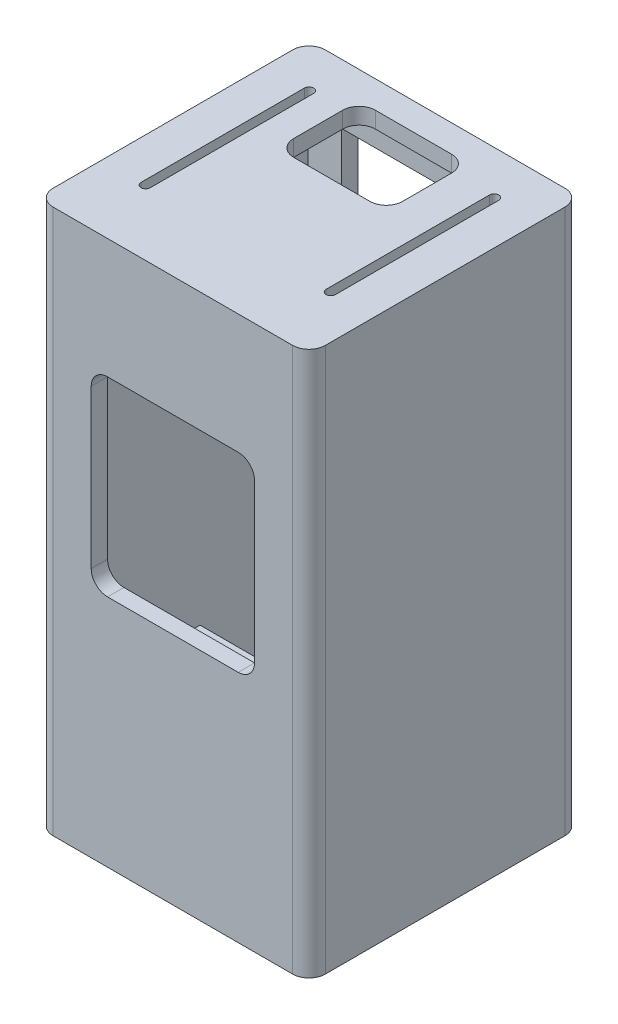
SolidWorks part; units mm, degrees
ref_plane "前视基准面" through (0, 0, 0) normal (0, 0, 1) x (1, 0, 0)
ref_plane "上视基准面" through (0, 0, 0) normal (0, 1, 0) x (1, 0, 0)
ref_plane "右视基准面" through (0, 0, 0) normal (1, 0, 0) x (0, 0, -1)
sketch "草图1" plane through (0, 0, 0) normal (0, 1, 0) x (1, 0, 0)
  line L1 (-25, 25) -> (25, 25)
  line L2 (-25, 25) -> (-25, -25)
  line L3 (-25, -25) -> (25, -25)
  line L4 (25, 25) -> (25, -25)
  point P4 (0, 0)
  dimension "D1" = 50
  dimension "D2" = 50
  dimension "D3" = 25
  dimension "D4" = 25
extrude "凸台-拉伸2" add sketch "草图1" along normal blind 100 contours L2 L1 L4 L3
fillet "圆角4" radius 3 4 edges at (25, 50, -25) (-25, 50, -25) (-25, 50, 25) (25, 50, 25)
sketch "草图3" plane through (0, 0, 0) normal (0, 1, 0) x (1, 0, 0)
  line L0 (-27.5, 0) -> (27.5, 0) construction
  line L1 (-22, 22) -> (22, 22)
  line L2 (-22, 22) -> (-22, -22)
  line L3 (-22, -22) -> (22, -22)
  line L4 (22, 22) -> (22, -22)
  dimension "D1" = 22
  dimension "D2" = 22
  dimension "D3" = 22
  dimension "D4" = 22
extrude "切除-拉伸4" cut sketch "草图3" along normal blind 80
extrude "凸台-拉伸4" add sketch "草图3<4>" along normal blind 20
sketch "草图3<4>" plane through (0, 0, 0) normal (0, 1, 0) x (1, 0, 0) same geometry as "草图3"
sketch "草图7" plane through (0, 0, 0) normal (0, 1, 0) x (1, 0, 0)
  line L0 (-22, 22) -> (-22, -22) construction
  line L1 (-22, -2) -> (22, -2)
  line L2 (-22, -2) -> (-22, -22)
  line L3 (-22, -22) -> (22, -22)
  line L4 (22, -2) -> (22, -22)
  dimension "D1" = 2
  dimension "D2" = 20
  dimension "D3" = 44
  dimension "D4" = 0
extrude "切除-拉伸5" cut sketch "草图7" along normal blind 20
extrude "凸台-拉伸5" add sketch "草图7<2>" along normal blind 5
sketch "草图7<2>" plane through (0, 0, 0) normal (0, 1, 0) x (1, 0, 0) same geometry as "草图7"
sketch "草图9" plane through (0, 0, 0) normal (0, 1, 0) x (1, 0, 0)
  line L0 (-22, 22) -> (-22, -22) construction
  line L1 (-22, 22) -> (22, 22)
  line L2 (-22, 22) -> (-22, 2)
  line L3 (-22, 2) -> (22, 2)
  line L4 (22, 22) -> (22, 2)
  point P4 (0, 2)
  dimension "D1" = 44
  dimension "D2" = 2
  dimension "D3" = 0
  dimension "D4" = 0
extrude "切除-拉伸6" cut sketch "草图9" along normal blind 20
extrude "凸台-拉伸6" add sketch "草图9<2>" along normal blind 3
sketch "草图9<2>" plane through (0, 0, 0) normal (0, 1, 0) x (1, 0, 0) same geometry as "草图9"
sketch "草图10" plane through (0, 0, 0) normal (0, 0, 1) x (1, 0, 0)
  line L0 (-12, 18) -> (-12, 12) construction
  line L1 (-11.15, 18) -> (-11.15, 12)
  line L2 (-12.85, 18) -> (-12.85, 12)
  line L4 (12, 18) -> (12, 12) construction
  line L5 (12.85, 18) -> (12.85, 12)
  line L6 (11.15, 18) -> (11.15, 12)
  arc A2 (-11.15, 18) -> (-12.85, 18) centre (-12, 18) ccw
  arc A3 (-12.85, 12) -> (-11.15, 12) centre (-12, 12) ccw
  arc A4 (12.85, 18) -> (11.15, 18) centre (12, 18) ccw
  arc A5 (11.15, 12) -> (12.85, 12) centre (12, 12) ccw
  point P0 (12, 15)
  point P4 (-12, 15)
  point P16 (0, 0)
  dimension "D2" = 12
  dimension "D3" = 12
  dimension "D1" = 18
  dimension "D4" = 18
extrude "切除-拉伸7" cut sketch "草图10" against normal blind 5 and the other way blind 5
ref_plane "基准面6" through (0, 110, 0) normal (0, 1, 0) x (1, 0, 0)
sketch "草图11" plane through (0, 110, 0) normal (0, 1, 0) x (1, 0, 0)
  line L0 (-17, 17) -> (-17, -13) construction
  line L1 (-16.15, 17) -> (-16.15, -13)
  line L2 (-17.85, 17) -> (-17.85, -13)
  line L3 (17, 17) -> (17, -13) construction
  line L4 (17.85, 17) -> (17.85, -13)
  line L5 (16.15, 17) -> (16.15, -13)
  line L6 (-22, 22) -> (-22, -22) construction
  line L7 (22, -22) -> (22, 22) construction
  line L10 (22, 22) -> (-22, 22) construction
  arc A0 (-16.15, 17) -> (-17.85, 17) centre (-17, 17) ccw
  arc A1 (-17.85, -13) -> (-16.15, -13) centre (-17, -13) ccw
  arc A2 (17.85, 17) -> (16.15, 17) centre (17, 17) ccw
  arc A3 (16.15, -13) -> (17.85, -13) centre (17, -13) ccw
  point P2 (-17, 2)
  point P7 (17, 2)
  point P14 (0, 0)
  point P17 (0, 0)
  point P20 (0, 0)
  point P23 (0, 0)
  dimension "D1" = 5
  dimension "D3" = 5
  dimension "D2" = 5
  dimension "D4" = 5
sketch "草图15" plane through (0, 110, 0) normal (0, 1, 0) x (1, 0, 0)
  line L4 (-22, -2) -> (22, -2)
  line L5 (-22, -2) -> (-22, -22)
  line L6 (-22, -22) -> (22, -22)
  line L7 (22, -2) -> (22, -22)
  dimension "D1" = 24
extrude "切除-拉伸9" cut sketch "草图15" against normal blind 41
extrude "凸台-拉伸7" add sketch "草图15<2>" against normal blind 15
sketch "草图15<2>" plane through (0, 110, 0) normal (0, 1, 0) x (1, 0, 0) same geometry as "草图15"
extrude "切除-拉伸10" cut sketch "草图15<3>" against normal blind 10
sketch "草图15<3>" plane through (0, 110, 0) normal (0, 1, 0) x (1, 0, 0) same geometry as "草图15"
sketch "草图16" plane through (0, 110, 0) normal (0, 1, 0) x (1, 0, 0)
  line L0 (-22.1977, 22) -> (21.8023, 22)
  line L1 (-22.1977, 22) -> (-22.1977, 2)
  line L2 (-22.1977, 2) -> (21.8023, 2)
  line L3 (21.8023, 22) -> (21.8023, 2)
  dimension "D1" = 0
extrude "切除-拉伸11" cut sketch "草图16" against normal blind 30
extrude "凸台-拉伸8" add sketch "草图16<2>" against normal blind 13
sketch "草图16<2>" plane through (0, 110, 0) normal (0, 1, 0) x (1, 0, 0) same geometry as "草图16"
extrude "切除-拉伸12" cut sketch "草图16<3>" against normal blind 10
sketch "草图16<3>" plane through (0, 110, 0) normal (0, 1, 0) x (1, 0, 0) same geometry as "草图16"
sketch "草图20" plane through (0, 0, 0) normal (0, 0, 1) x (1, 0, 0)
  line L0 (-12, 90) -> (-12, 82) construction
  line L1 (-11.15, 90) -> (-11.15, 82)
  line L2 (-12.85, 90) -> (-12.85, 82)
  line L3 (12, 90) -> (12, 82) construction
  line L4 (12.85, 90) -> (12.85, 82)
  line L5 (11.15, 90) -> (11.15, 82)
  line L6 (-22, 100) -> (22, 100) construction
  line L7 (22, 80) -> (-22, 80) construction
  line L8 (-22, 80) -> (21.8023, 80) construction
  arc A0 (-11.15, 90) -> (-12.85, 90) centre (-12, 90) ccw
  arc A1 (-12.85, 82) -> (-11.15, 82) centre (-12, 82) ccw
  arc A2 (12.85, 90) -> (11.15, 90) centre (12, 90) ccw
  arc A3 (11.15, 82) -> (12.85, 82) centre (12, 82) ccw
  point P0 (12, 86)
  point P4 (-12, 86)
  dimension "D1" = 10
  dimension "D2" = 10
  dimension "D3" = 2
  dimension "D4" = 2
extrude "切除-拉伸17" cut sketch "草图11" against normal blind 40
extrude "切除-拉伸18" cut sketch "草图20" against normal blind 4 and the other way blind 5
sketch "草图21" plane through (0, 110, 0) normal (0, 1, 0) x (1, 0, 0)
  line L0 (16.15, -2) -> (-16.15, -2) construction
  line L1 (-10.8088, 20) -> (9.1912, 20)
  line L2 (-10.8088, 20) -> (-10.8088, 5)
  line L3 (-10.8088, 5) -> (9.1912, 5)
  line L4 (9.1912, 20) -> (9.1912, 5)
  line L5 (22, -22) -> (22, -2) construction
  dimension "D1" = 22
  dimension "D2" = 15
  dimension "D3" = 20
  dimension "D4" = 12.8088
extrude "切除-拉伸19" cut sketch "草图21" against normal blind 44
sketch "草图23" plane through (0, 0, 0) normal (0, 0, 1) x (1, 0, 0)
  line L0 (22, 0) -> (22, 100) construction
  line L1 (-16, 92) -> (16, 92)
  line L2 (-16, 92) -> (-16, 20)
  line L3 (-16, 20) -> (16, 20)
  line L4 (16, 92) -> (16, 20)
  dimension "D1" = 72
  dimension "D2" = 32
  dimension "D3" = 20
  dimension "D4" = 6
extrude "切除-拉伸20" cut sketch "草图23" against normal blind 44
sketch "草图25" plane through (0, 0, 0) normal (0, 0, 1) x (1, 0, 0)
  line L0 (-22, 100) -> (-22, 0) construction
  line L1 (-15, 78) -> (15, 78)
  line L2 (-15, 78) -> (-15, 43)
  line L3 (-15, 43) -> (15, 43)
  line L4 (15, 78) -> (15, 43)
  arc A0 (-11.15, 18) -> (-12.85, 18) centre (-12, 18) ccw construction
  dimension "D1" = 25
  dimension "D2" = 30
  dimension "D3" = 35
  dimension "D4" = 7
extrude "切除-拉伸21" cut sketch "草图25" along normal blind 40
fillet "圆角5" radius 3 4 edges at (-15, 43, 23.5) (15, 43, 23.5) (15, 78, 23.5) (-15, 78, 23.5)
fillet "圆角6" radius 3 4 edges at (-10.8088, 98.5, -5) (-10.8088, 98.5, -20) (9.1912, 98.5, -20) (9.1912, 98.5, -5)
